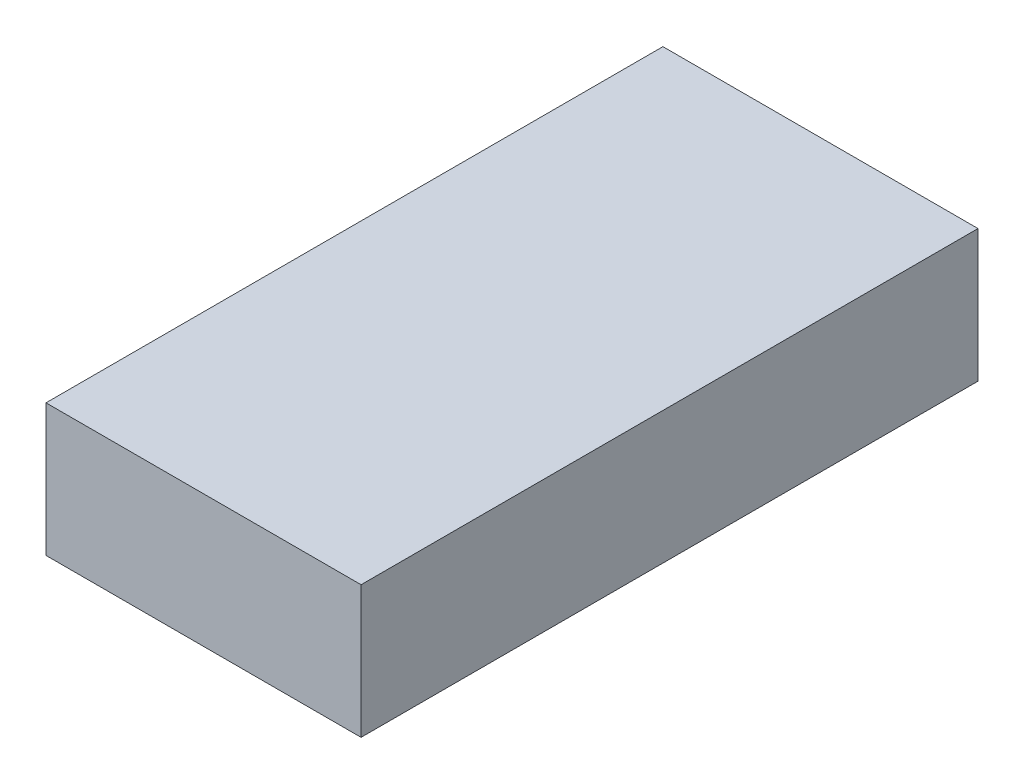
SolidWorks part; units mm, degrees
ref_plane "Front Plane" through (0, 0, 0) normal (0, 0, 1) x (1, 0, 0)
ref_plane "Top Plane" through (0, 0, 0) normal (0, 1, 0) x (1, 0, 0)
ref_plane "Right Plane" through (0, 0, 0) normal (1, 0, 0) x (0, 0, -1)
sketch "Sketch1" plane through (0, 0, 0) normal (0, 1, 0) x (1, 0, 0)
  line L0 (-5.65, 12.5) -> (-5.65, 14)
  line L1 (7.15, 14) -> (-7.15, 14)
  line L2 (7.15, 14) -> (7.15, -14)
  line L3 (7.15, -14) -> (-7.15, -14)
  line L4 (-7.15, 14) -> (-7.15, -14)
  line L5 (7.15, 14) -> (-7.15, -14) construction
  line L6 (7.15, -14) -> (-7.15, 14) construction
  line L7 (5.65, 12.5) -> (-5.65, 12.5)
  line L8 (5.65, 12.5) -> (5.65, -12.5)
  line L9 (5.65, -12.5) -> (-5.65, -12.5)
  line L10 (-5.65, 12.5) -> (-5.65, -12.5)
  line L11 (5.65, 12.5) -> (-5.65, -12.5) construction
  line L12 (5.65, -12.5) -> (-5.65, 12.5) construction
  line L15 (5.65, 14) -> (5.65, 12.5)
  point P0 (0, 0)
  point P6 (0, 0)
  dimension "D1" = 14.3
  dimension "D2" = 1.5
  dimension "D3" = 1.5
  dimension "D4" = 28
extrude "Boss-Extrude1" add sketch "Sketch1" along normal blind 4 contours L1 L15 L8 L9 L10 L0 L4 L3 L2 region at (-5.9644, 0, 0)
sketch "Sketch2" plane through (0, 4, 0) normal (0, 1, 0) x (1, 0, 0)
  line L1 (-7.15, 14) -> (7.15, 14)
  line L2 (-7.15, 14) -> (-7.15, -14)
  line L3 (-7.15, -14) -> (7.15, -14)
  line L4 (7.15, 14) -> (7.15, -14)
extrude "Boss-Extrude2" add sketch "Sketch2" along normal blind 2
